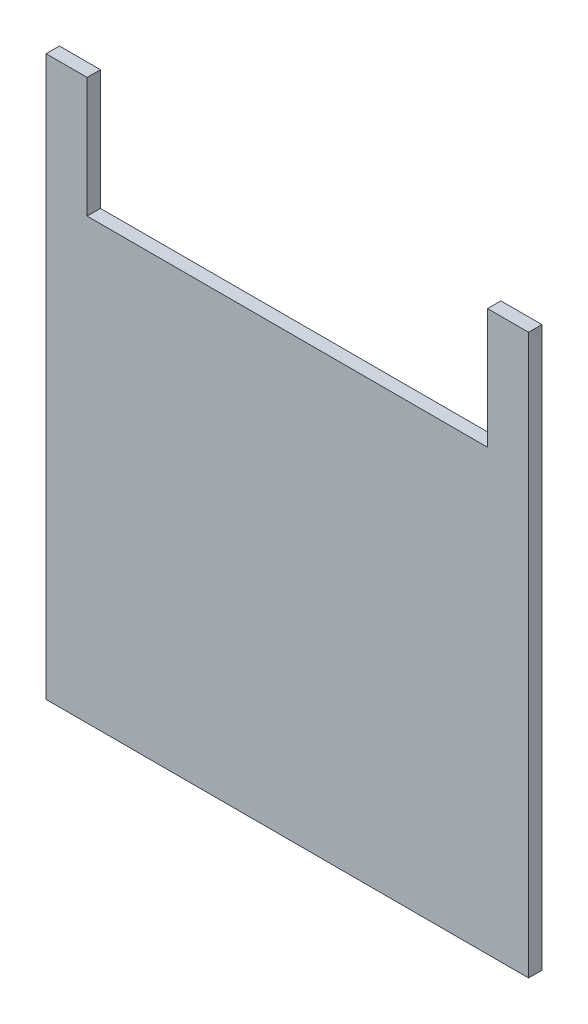
SolidWorks part; units mm, degrees
material "Beech"
ref_plane "Front Plane" through (0, 0, 0) normal (0, 0, 1) x (1, 0, 0)
ref_plane "Top Plane" through (0, 0, 0) normal (0, 1, 0) x (1, 0, 0)
ref_plane "Right Plane" through (0, 0, 0) normal (1, 0, 0) x (0, 0, -1)
sketch "Sketch1" plane through (0, 0, 0) normal (0, 0, 1) x (1, 0, 0)
  line L1 (361.5, -419) -> (-361.5, -419)
  line L2 (361.5, -419) -> (361.5, 419)
  line L3 (361.5, 419) -> (-361.5, 419)
  line L4 (-361.5, -419) -> (-361.5, 419)
  line L5 (361.5, -419) -> (-361.5, 419) construction
  line L6 (361.5, 419) -> (-361.5, -419) construction
  point P0 (0, 0)
  dimension "D1" = 723
  dimension "D2" = 838
extrude "Boss-Extrude1" add sketch "Sketch1" along normal blind 20
sketch "Sketch2" plane through (0, 0, 20) normal (0, 0, 1) x (1, 0, 0)
  line L1 (-300, 419) -> (300, 419)
  line L2 (-300, 419) -> (-300, 239)
  line L3 (-300, 239) -> (300, 239)
  line L4 (300, 419) -> (300, 239)
  line L5 (361.5, 419) -> (-361.5, 419) construction
  line L6 (0, 239) -> (0, 0) construction
  dimension "D1" = 180
  dimension "D2" = 600
extrude "Cut-Extrude1" cut sketch "Sketch2" against normal up to next
